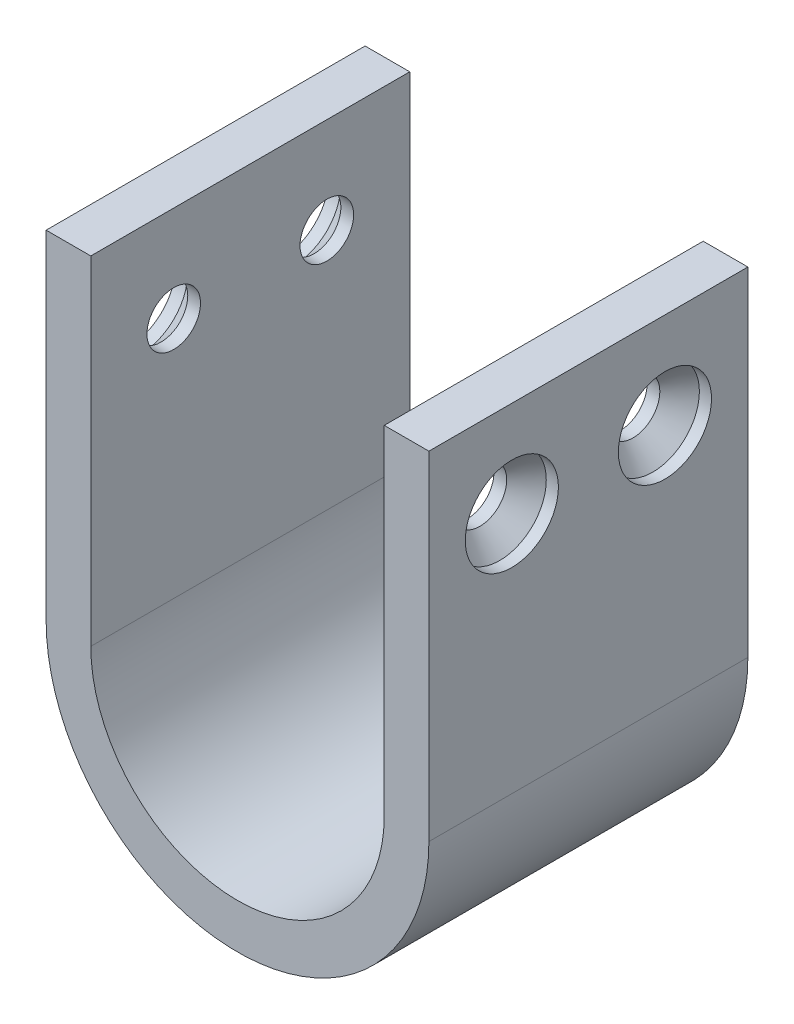
SolidWorks part; units mm, degrees
ref_plane "Спереди" through (0, 0, 0) normal (0, 0, 1) x (1, 0, 0)
ref_plane "Сверху" through (0, 0, 0) normal (0, 1, 0) x (1, 0, 0)
ref_plane "Справа" through (0, 0, 0) normal (1, 0, 0) x (0, 0, -1)
sketch "Эскиз\\ основы с торца" plane through (0, 0, 0) normal (0, 0, 1) x (1, 0, 0)
  line L0 (0, 0) -> (0, 38.9225) construction
  line L1 (0, 0) -> (29.937, 0) construction
  line L23 (-11.5, 0) -> (-11.5, 26.5)
  line L29 (15, 0) -> (15, 26.5)
  line L30 (11.5, 0) -> (11.5, 26.5)
  line L31 (-15, 0) -> (-15, 26.5)
  line L38 (-15, 26.5) -> (-11.5, 26.5)
  line L39 (15, 26.5) -> (11.5, 26.5)
  arc A5 (-15, 0) -> (15, 0) centre (0, 0) ccw
  arc A10 (-11.5, 0) -> (11.5, 0) centre (0, 0) ccw
  dimension "D3" = 26.5
  dimension "D1" = 23
  dimension "D2" = 15
extrude "Основа" add sketch "Эскиз\\ основы с торца" along normal blind 25
sketch "Эскиз отверстий" plane through (-15, 0, 0) normal (-1, 0, 0) x (0, 0, 1)
  line L0 (0, 19) -> (25, 19) construction
  line L4 (12.5, 26.5) -> (12.5, 19) construction
  line L5 (25, 26.5) -> (25, 0) construction
  line L6 (0, -50) -> (0, 50) construction
  line L7 (25, 26.5) -> (0, 26.5) construction
  circle A1 centre (6.5, 19) radius 2.1
  circle A2 centre (18.5, 19) radius 2.1
  circle A3 centre (6.5, 19) radius 3.65
  circle A4 centre (18.5, 19) radius 3.65
  dimension "D2" = 4.2
  dimension "D4" = 7.3
  dimension "D1" = 7.5
  dimension "D3" = 6
extrude "отверстия" cut sketch "Эскиз отверстий" against normal up to next contours A1 | A2 region at (-15, 19, 6.5) region at (-15, 19, 18.5)
extrude "Вырез под потайную шляпку" cut sketch "Эскиз2<3>" against normal blind 0.5
sketch "Эскиз2<3>" plane through (-15, 0, 0) normal (-1, 0, 0) x (0, 0, 1) same geometry as "Эскиз отверстий"
chamfer "Фаска под шляпку" distance 2 angle 45 2 edges at (-14.5, 19, 16.4) (-14.5, 19, 8.6)
mirror "Дублирование отверстий" about plane through (0, 0, 0) normal (1, 0, 0) of "Фаска под шляпку", "Вырез под потайную шляпку", "отверстия"
